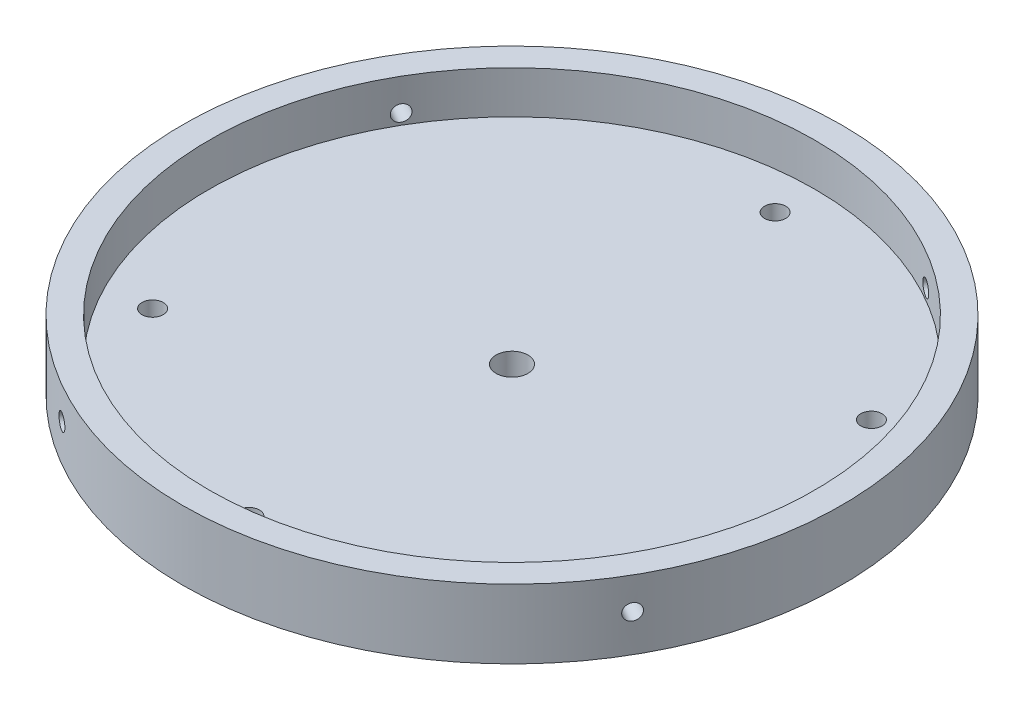
SolidWorks part; units mm, degrees
ref_plane "Front Plane" through (0, 0, 0) normal (0, 0, 1) x (1, 0, 0)
ref_plane "Top Plane" through (0, 0, 0) normal (0, 1, 0) x (1, 0, 0)
ref_plane "Right Plane" through (0, 0, 0) normal (1, 0, 0) x (0, 0, -1)
sketch "Sketch1" plane through (0, 0, 0) normal (0, 1, 0) x (1, 0, 0)
  circle A0 centre (0, 0) radius 62
  dimension "D1" = 124
extrude "Boss-Extrude1" add sketch "Sketch1" along normal blind 5
sketch "Sketch2" plane through (0, 5, 0) normal (0, 1, 0) x (1, 0, 0)
  circle A0 centre (0, 49.5) radius 2
  dimension "D2" = 4
  dimension "D1" = 49.5
extrude "Cut-Extrude1" cut sketch "Sketch2" against normal blind 5 contours A0
pattern_circular "CirPattern1" count 2 every 120 about axis through (0, 5, 0) along (0, 1, 0) of "Cut-Extrude1"
sketch "Sketch4" plane through (0, 5, 0) normal (0, 1, 0) x (1, 0, 0)
  line L0 (0, 49.5) -> (-42.8683, -24.75) construction
  line L1 (0, 0) -> (-23.6703, -40.9981) construction
ref_plane "Plane1" through (0, 0, 0) normal (-0.866, 0, -0.5) x (-0.5, 0, 0.866)
mirror "Mirror1" about plane through (0, 0, 0) normal (-0.866, 0, -0.5) of "Cut-Extrude1", "CirPattern1"
sketch "Sketch5" plane through (0, 5, 0) normal (0, 1, 0) x (1, 0, 0)
  circle A0 centre (0, 0) radius 62
  circle A1 centre (0, 0) radius 57
  dimension "D1" = 5
extrude "Boss-Extrude2" add sketch "Sketch5" along normal blind 8
sketch "Sketch6" plane through (0, 0, 0) normal (-0.866, 0, -0.5) x (-0.5, 0, 0.866)
  line L0 (57, 13) -> (-57, 13) construction
  circle A0 centre (0, 7) radius 1.5
  dimension "D1" = 3
  dimension "D2" = 6
extrude "Cut-Extrude2" cut sketch "Sketch6" against normal blind 90 and the other way blind 102 contours A0
pattern_circular "CirPattern2" count 2 every 90 about axis through (0, 13, 0) along (0, 1, 0) of "Cut-Extrude2"
sketch "Sketch7" plane through (0, 5, 0) normal (0, 1, 0) x (1, 0, 0)
  circle A0 centre (0, 0) radius 3
  dimension "D1" = 6
extrude "Cut-Extrude3" cut sketch "Sketch7" against normal blind 10
